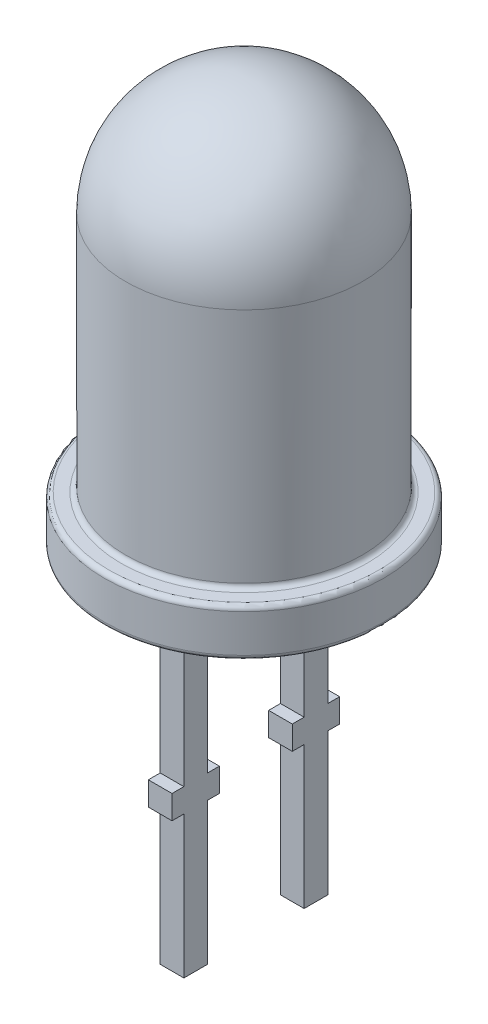
SolidWorks part; units mm, degrees
ref_plane "Спереди" through (0, 0, 0) normal (0, 0, 1) x (1, 0, 0)
ref_plane "Сверху" through (0, 0, 0) normal (0, 1, 0) x (1, 0, 0)
ref_plane "Справа" through (0, 0, 0) normal (1, 0, 0) x (0, 0, -1)
sketch "Эскиз1" plane through (0, 0, 0) normal (1, 0, 0) x (0, 0, -1)
  line L0 (4.8309, 0) -> (-4.1566, 0) construction
  line L1 (4.8309, 4) -> (-4.1566, 4) construction
  line L2 (0, -8.9757) -> (0, 8.1567) construction
  line L3 (-1.27, 7.7097) -> (-1.27, -11.3357) construction
  line L4 (-1.52, 4) -> (-1.52, 0.5)
  line L5 (-1.52, 0.5) -> (-1.77, 0.5)
  line L6 (-1.77, 0.5) -> (-1.77, 0)
  line L7 (-1.77, 0) -> (-1.52, 0)
  line L8 (-1.52, 0) -> (-1.52, -3)
  line L9 (-1.52, -3) -> (-1.02, -3)
  line L10 (-1.02, 0.5) -> (-1.02, 0) construction
  line L11 (-1.52, 0.5) -> (-1.52, 0) construction
  line L12 (-1.02, 0) -> (-1.02, -3)
  line L13 (-0.77, 0) -> (-1.02, 0)
  line L14 (-0.77, 0.5) -> (-0.77, 0)
  line L15 (-1.02, 0.5) -> (-0.77, 0.5)
  line L16 (-1.02, 4) -> (-1.02, 0.5)
  line L17 (1.52, 0.5) -> (1.52, 0) construction
  line L18 (1.02, 0.5) -> (1.02, 0) construction
  line L19 (1.02, 4) -> (1.02, 0.5)
  line L20 (1.02, 0.5) -> (0.77, 0.5)
  line L21 (0.77, 0.5) -> (0.77, 0)
  line L22 (0.77, 0) -> (1.02, 0)
  line L23 (1.02, 0) -> (1.02, -3)
  line L24 (1.52, -3) -> (1.02, -3)
  line L25 (1.52, 0) -> (1.52, -3)
  line L26 (1.77, 0) -> (1.52, 0)
  line L27 (1.77, 0.5) -> (1.77, 0)
  line L28 (1.52, 0.5) -> (1.77, 0.5)
  line L29 (1.52, 4) -> (1.52, 0.5)
  line L30 (-3.3588, 8) -> (3.258, 8) construction
  line L31 (1.52, 4) -> (1.52, 4.1)
  line L32 (1.62, 4.2) -> (1.72, 4.2)
  line L33 (1.82, 4.3) -> (1.82, 5.1764)
  line L34 (1.8094, 5.2211) -> (1.3647, 6.1106)
  line L35 (1.4094, 6.2447) -> (1.7549, 6.4174)
  line L36 (1.8101, 6.5069) -> (1.8101, 8)
  line L37 (1.8101, 8) -> (-0.7899, 8)
  line L38 (-0.7899, 8) -> (-0.7899, 7.4009)
  line L39 (-0.7423, 7.3158) -> (0.6225, 6.4744)
  line L40 (0.67, 6.3892) -> (0.67, 5.1594)
  line L41 (0.7221, 5.0716) -> (1.1027, 4.864)
  line L42 (1.1255, 4.7055) -> (1.0493, 4.6293)
  line L43 (1.02, 4.5586) -> (1.02, 4)
  line L44 (-1.02, 4) -> (-1.02, 4.5)
  line L45 (-0.92, 4.6) -> (-0.27, 4.6)
  line L46 (-0.17, 4.7) -> (-0.17, 5.9)
  line L47 (-0.07, 6) -> (0.03, 6)
  line L48 (0.13, 6.1) -> (0.13, 6.2408)
  line L49 (0.0825, 6.3259) -> (-1.0365, 7.0158)
  line L50 (-1.0841, 7.1009) -> (-1.0841, 8.1)
  line L51 (-1.0841, 8.1) -> (-1.7066, 8.1)
  line L52 (-1.7066, 8.1) -> (-1.7066, 6.8009)
  line L53 (-1.6591, 6.7158) -> (-1.2675, 6.4744)
  line L54 (-1.22, 6.3892) -> (-1.22, 6.05)
  line L55 (-1.26, 5.97) -> (-1.78, 5.58)
  line L56 (-1.82, 5.5) -> (-1.82, 4.3)
  line L57 (-1.72, 4.2) -> (-1.62, 4.2)
  line L58 (-1.52, 4.1) -> (-1.52, 4)
  line L59 (1.52, 4.2) -> (-2.5199, 4.2) construction
  line L60 (-0.17, 4.6) -> (2.6617, 4.6) construction
  line L61 (1.8101, 6.4451) -> (-2.4556, 6.4451) construction
  line L62 (0.13, 6) -> (-2.5199, 6) construction
  arc A0 (1.82, 4.3) -> (1.72, 4.2) centre (1.72, 4.3) cw
  arc A1 (1.52, 4.1) -> (1.62, 4.2) centre (1.62, 4.1) cw
  arc A2 (-0.7899, 7.4009) -> (-0.7423, 7.3158) centre (-0.6899, 7.4009) ccw
  arc A3 (0.6225, 6.4744) -> (0.67, 6.3892) centre (0.57, 6.3892) cw
  arc A4 (0.67, 5.1594) -> (0.7221, 5.0716) centre (0.77, 5.1594) ccw
  arc A5 (1.8101, 6.5069) -> (1.7549, 6.4174) centre (1.7101, 6.5069) cw
  arc A6 (1.4094, 6.2447) -> (1.3647, 6.1106) centre (1.4542, 6.1553) ccw
  arc A7 (1.8094, 5.2211) -> (1.82, 5.1764) centre (1.72, 5.1764) cw
  arc A8 (1.02, 4.5586) -> (1.0493, 4.6293) centre (1.12, 4.5586) cw
  arc A9 (1.1027, 4.864) -> (1.1255, 4.7055) centre (1.0548, 4.7762) cw
  arc A10 (-1.0841, 7.1009) -> (-1.0365, 7.0158) centre (-0.9841, 7.1009) ccw
  arc A11 (-1.7066, 6.8009) -> (-1.6591, 6.7158) centre (-1.6066, 6.8009) ccw
  arc A12 (-1.2675, 6.4744) -> (-1.22, 6.3892) centre (-1.32, 6.3892) cw
  arc A13 (-1.22, 6.05) -> (-1.26, 5.97) centre (-1.32, 6.05) cw
  arc A14 (-1.78, 5.58) -> (-1.82, 5.5) centre (-1.72, 5.5) ccw
  arc A15 (-1.82, 4.3) -> (-1.72, 4.2) centre (-1.72, 4.3) ccw
  arc A16 (-1.62, 4.2) -> (-1.52, 4.1) centre (-1.62, 4.1) cw
  arc A17 (-1.02, 4.5) -> (-0.92, 4.6) centre (-0.92, 4.5) cw
  arc A18 (-0.27, 4.6) -> (-0.17, 4.7) centre (-0.27, 4.7) ccw
  arc A19 (-0.17, 5.9) -> (-0.07, 6) centre (-0.07, 5.9) cw
  arc A20 (0.0825, 6.3259) -> (0.13, 6.2408) centre (0.03, 6.2408) cw
  arc A21 (0.13, 6.1) -> (0.03, 6) centre (0.03, 6.1) cw
  point P19 (-1.27, -3)
  point P34 (1.27, -3)
  point P69 (1.82, 4.2)
  point P75 (-0.7899, 7.3451)
  point P78 (0.67, 6.4451)
  point P81 (0.67, 5.1)
  point P87 (1.32, 6.2)
  point P90 (1.82, 5.2)
  point P93 (1.02, 4.6)
  point P96 (1.22, 4.8)
  point P99 (-1.0841, 7.0451)
  point P102 (-1.7066, 6.7451)
  point P105 (-1.22, 6.4451)
  point P108 (-1.22, 6)
  point P111 (-1.82, 5.55)
  point P114 (-1.82, 4.2)
  point P119 (-1.02, 4.6)
  point P125 (-0.17, 6)
  point P128 (0.13, 6.2966)
  dimension "D30" = 0.1
  dimension "D1" = 4
  dimension "D2" = 1.27
  dimension "D3" = 0.5
  dimension "D4" = 1
  dimension "D5" = 0.5
  dimension "D6" = 3
  dimension "D7" = 0.3
  dimension "D8" = 0.2
  dimension "D9" = 0.4
  dimension "D10" = 1
  dimension "D11" = 0.5
  dimension "D12" = 0.2
  dimension "D13" = 4
  dimension "D14" = 2
  dimension "D15" = 2.2451
  dimension "D16" = 0.5
  dimension "D17" = 0.2
  dimension "D18" = 0.35
  dimension "D19" = 2.6
  dimension "D20" = 0.9
  dimension "D21" = 0.85
  dimension "D22" = 0.3
  dimension "D23" = 0.2966
  dimension "D24" = 1.8
  dimension "D25" = 1.35
  dimension "D26" = 0.6
  dimension "D27" = 0.3
  dimension "D28" = 0.6
  dimension "D29" = 0.1
extrude "Бобышка-Вытянуть1" add sketch "Эскиз1" along normal blind 0.25 and the other way blind 0.25
sketch "Эскиз2" plane through (0, 0, 0) normal (1, 0, 0) x (0, 0, -1)
  line L0 (0, 0) -> (0, 9.0521) construction
  line L1 (0, 8.0012) -> (-0.6, 8.0012)
  line L2 (-0.6, 8.0012) -> (-0.6, 7.8012)
  line L3 (-0.6, 7.8012) -> (0, 7.0012)
  line L4 (0, 7.0012) -> (0, 8.0012)
  dimension "D1" = 1.2
  dimension "D2" = 0.2
  dimension "D3" = 1
  dimension "D4" = 8.0012
revolve "Повернуть2" add sketch "Эскиз2" angle 360 about L0
sketch "Эскиз3" plane through (0, 0, 0) normal (1, 0, 0) x (0, 0, -1)
  line L0 (0, 8.0047) -> (0.55, 8.0047)
  line L1 (0.55, 8.0047) -> (0.55, 7.9947)
  line L2 (0.55, 7.9947) -> (0.15, 7.9047)
  line L3 (0.15, 7.9047) -> (0, 7.9047)
  line L4 (0, -8.9757) -> (0, 8.1567) construction
  line L5 (0, 7.9047) -> (0, 8.0047)
  dimension "D1" = 8.0047
  dimension "D2" = 0.15
  dimension "D3" = 0.01
  dimension "D4" = 0.1
  dimension "D5" = 0.55
revolve "Вырез-Повернуть1" cut sketch "Эскиз3" angle 360 about L2
sketch "Эскиз4" plane through (0, 7.9047, 0) normal (0, 1, 0) x (1, 0, 0)
  line L1 (-0.1, -0.1) -> (0.1, -0.1)
  line L2 (-0.1, -0.1) -> (-0.1, 0.1)
  line L3 (-0.1, 0.1) -> (0.1, 0.1)
  line L4 (0.1, -0.1) -> (0.1, 0.1)
  line L5 (-0.1, -0.1) -> (0.1, 0.1) construction
  line L6 (-0.1, 0.1) -> (0.1, -0.1) construction
  point P0 (0, 0)
  dimension "D1" = 0.2
  dimension "D2" = 0.2
extrude "Бобышка-Вытянуть2" add sketch "Эскиз4" along normal blind 0.05
sketch "Эскиз6" plane through (0, 7.9547, 0) normal (0, 1, 0) x (1, 0, 0)
  circle A0 centre (0, 0) radius 0.02
  dimension "D1" = 0.04
sketch3d "Трехмерный эскиз2"
  line L0 (0, 7.9547, 0) -> (0, 7.9673, 0)
  line L1 (0, -8.9757, 0) -> (0, 8.1567, 0) construction
  line L2 (-0.25, 8.1, 1.7066) -> (0.25, 8.1, 1.0841) construction
  line L3 (-0.25, 8.1, 1.0841) -> (0.25, 8.1, 1.7066) construction
  line L4 (0, 8.1, 1.3953) -> (0, 8.1042, 1.3953)
  line L5 (0, 8.154, 1.3497) -> (0, 8.1964, 0.8702)
  line L6 (0, 8.163, 0.536) -> (0, 8.0153, 0.0358)
  arc A0 (0, 7.9673, 0) -> (0, 8.0153, 0.0358) centre (0, 7.9673, 0.05) ccw
  arc A1 (0, 8.1042, 1.3953) -> (0, 8.154, 1.3497) centre (0, 8.1042, 1.3453) ccw
  arc A2 (0, 8.163, 0.536) -> (0, 8.1964, 0.8702) centre (0, 7.2999, 0.7909) ccw
  point P18 (0, 8.0047, 0)
  point P19 (0.05, 7.9673, 0.05)
  point P22 (0, 8.15, 1.3953)
  point P23 (-0.05, 8.1042, 1.3453)
  point P26 (0, 8.2115, 0.6999)
  point P27 (0.9, 7.2999, 0.7909)
  dimension "D3" = 0.05
  dimension "D4" = 0.9
  dimension "D1" = 0.05
  dimension "D2" = 0.05
sweep "По траектории1" add profiles "Эскиз6" path "Трехмерный эскиз2"
sketch "Эскиз7" plane through (0, 0, 0) normal (1, 0, 0) x (0, 0, -1)
  line L0 (0, 4) -> (2.95, 4)
  line L1 (4.8309, 4) -> (-4.1566, 4) construction
  line L2 (0, -8.9757) -> (0, 8.1567) construction
  line L3 (2.95, 4) -> (2.95, 5)
  line L4 (2.95, 5) -> (2.5, 5)
  line L5 (2.5, 5) -> (2.5, 10.1)
  line L6 (0, 0) -> (0, 13.3429) construction
  line L7 (0, 12.6) -> (0, 12.5025)
  line L8 (0, 4.1) -> (2.85, 4.1)
  line L9 (2.85, 4.1) -> (2.85, 4.9)
  line L10 (2.85, 4.9) -> (2.4025, 4.9)
  line L11 (2.4025, 4.9) -> (2.4025, 10.1)
  line L12 (0, 4.1) -> (0, 4)
  line L13 (0, 10.1) -> (4.3229, 10.1) construction
  arc A0 (2.5, 10.1) -> (0, 12.6) centre (0, 10.1) ccw
  arc A1 (2.4025, 10.1) -> (0, 12.5025) centre (0, 10.1) ccw
  dimension "D1" = 2.5
  dimension "D2" = 8.6
  dimension "D3" = 1
  dimension "D4" = 5
  dimension "D5" = 5.9
  dimension "D6" = 0.1
  dimension "D7" = 0.1
  dimension "D8" = 0.1
  dimension "D9" = 0.0975
  dimension "D10" = 0.0975
revolve "Повернуть3" add sketch "Эскиз7" angle 360 about L6
fillet "Скругление1" radius 0.1 3 edges at (0, 5, -2.5) (0, 4, -2.95) (0, 5, -2.95)
fillet "Скругление2" radius 0.1 8 edges at (0, 4, 1.02) (0, 4, 1.52) (0.25, 4, 1.27) (-0.25, 4, 1.27) (0, 4, -1.52) (-0.25, 4, -1.27) (0, 4, -1.02) (0.25, 4, -1.27)
ref_point "Point1"
ref_point "Point2"
ref_axis "Axis1" through (0, -3, -1.27) along (0, -1, 0)
ref_axis "Axis2" through (0, -3, 1.27) along (0, -1, 0)
equation "\"D10@Эскиз7\"=\"D1@Эскиз7\"-0.1"
